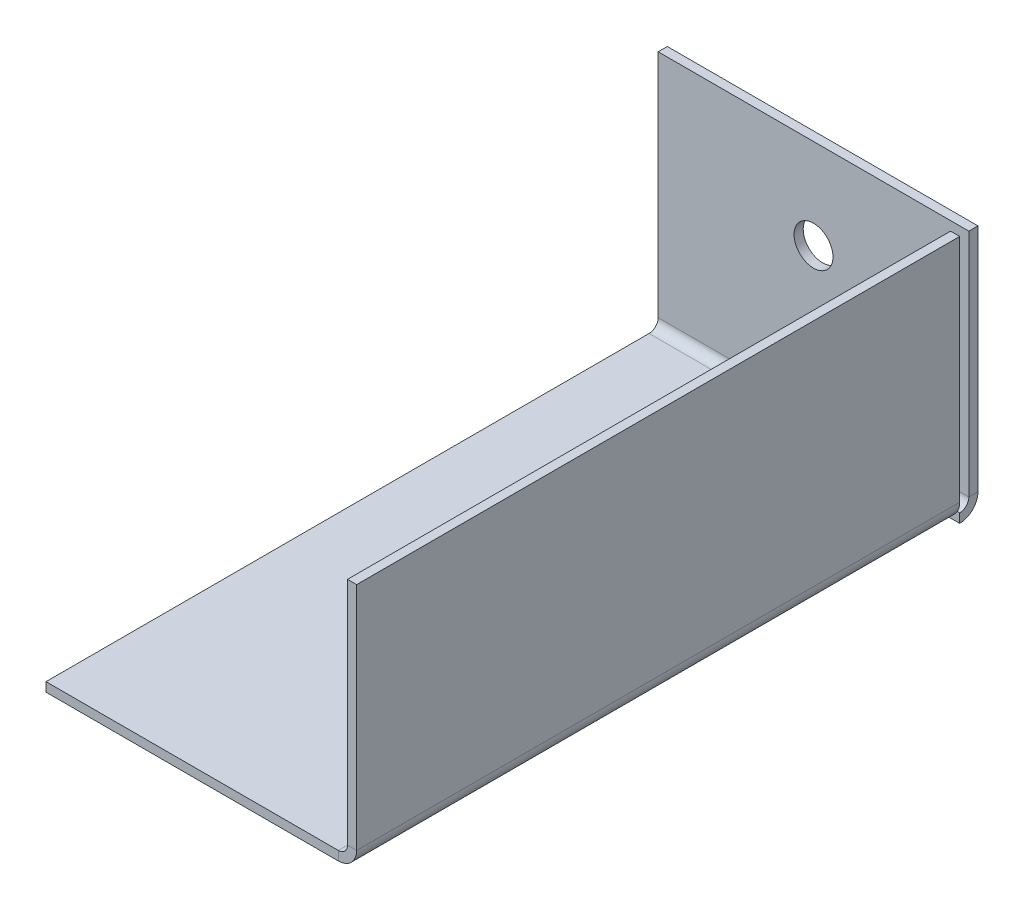
SolidWorks part; units mm, degrees
note: The reader was unsure of these and kept them because the rebuilt part matched: flange length of "Edge-Flange1", "Edge-Flange3".
ref_plane "Front Plane" through (0, 0, 0) normal (0, 0, 1) x (1, 0, 0)
ref_plane "Top Plane" through (0, 0, 0) normal (0, 1, 0) x (1, 0, 0)
ref_plane "Right Plane" through (0, 0, 0) normal (1, 0, 0) x (0, 0, -1)
sketch "Sketch1" plane through (0, 0, 0) normal (0, 1, 0) x (1, 0, 0)
  line L1 (-12.5, -25) -> (12.5, -25)
  line L2 (-12.5, -25) -> (-12.5, 25)
  line L3 (-12.5, 25) -> (12.5, 25)
  line L4 (12.5, -25) -> (12.5, 25)
  line L5 (-12.5, -25) -> (12.5, 25) construction
  line L6 (-12.5, 25) -> (12.5, -25) construction
  point P0 (0, 0)
  dimension "D1" = 50
  dimension "D2" = 25
base flange "Base-Flange1" sketch "Sketch1" thickness 0.7366 reverse thickness direction no parameters "D1"=0.7366
edge flange "Edge-Flange1" sketch "Sketch8" flange angle 90 flange length 20 flange position material inside bend radius 0.7366 thickness 0.7366 relief rectangular parameters "D6"=10
sketch "Sketch8" plane through (0, 0, -25) normal (0, 0, -1) x (-1, 0, 0)
  line L0 (-12.5, 0) -> (12.5, 0) construction
  line L1 (-12.5, 0) -> (12.5, 0)
  line L2 (-12.5, 0) -> (-12.5, 19.2634)
  line L3 (-12.5, 19.2634) -> (12.5, 19.2634)
  line L4 (12.5, 19.2634) -> (12.5, 0)
  circle A0 centre (0, 12) radius 1.565
  dimension "D1" = 3.13
  dimension "D2" = 12.5
  dimension "D3" = 12
bend "EdgeBend1" bend radius 0.7366 bend angle 90 parameters "D5"=1
edge flange "Edge-Flange3" sketch "Sketch14" flange angle 90 flange length 20 flange position material inside bend radius 0.7366 thickness 0.7366 relief none parameters "D6"=10
sketch "Sketch14" plane through (12.5, 0, 0) normal (1, 0, 0) x (0, 0, -1)
  line L0 (-25, 0) -> (23.5268, 0) construction
  line L1 (-25, 0) -> (23.5268, 0)
  line L2 (-25, 0) -> (-25, 19.2634)
  line L3 (-25, 19.2634) -> (23.5268, 19.2634)
  line L4 (23.5268, 19.2634) -> (23.5268, 0)
bend "EdgeBend3" bend radius 0.7366 bend angle 90 parameters "D5"=2
sketch "Bend-Lines1" plane through (0, 0, 0) normal (0, 1, 0) x (1, 0, 0)
sketch "Bounding-Box1" plane through (0, 0, 0) normal (0, 1, 0) x (1, 0, 0)
sheet metal parameters "Sheet-Metal1" thickness 0.7366 parameters "D1"=0.7366
flat pattern "Flat-Pattern1" [suppressed]
sketch "Bend-Lines2" plane through (0, 0, 0) normal (0, 1, 0) x (1, 0, 0)
sketch "Bounding-Box2" [suppressed] plane through (0, 0, 0) normal (0, 1, 0) x (1, 0, 0)
sheet metal parameters "Sheet-Metal2" thickness 0.7366 parameters "D1"=0.7366
flat pattern "Flat-Pattern1" [suppressed]
sketch "Bend-Lines2" plane through (0, 0, 0) normal (0, 1, 0) x (1, 0, 0)
sketch "Bounding-Box2" [suppressed] plane through (0, 0, 0) normal (0, 1, 0) x (1, 0, 0)
bend of the flat pattern "Flatten-<EdgeBend1>1"
sheet metal parameters "Sheet-Metal4" thickness 0.7366 parameters "D1"=0.7366
flat pattern "Flat-Pattern1" [suppressed]
sketch "Bend-Lines2" plane through (0, 0, 0) normal (0, 1, 0) x (1, 0, 0)
sketch "Bounding-Box2" [suppressed] plane through (0, 0, 0) normal (0, 1, 0) x (1, 0, 0)
bend of the flat pattern "Flatten-<EdgeBend1>1"
bend of the flat pattern "Flatten-<EdgeBend3>1"
